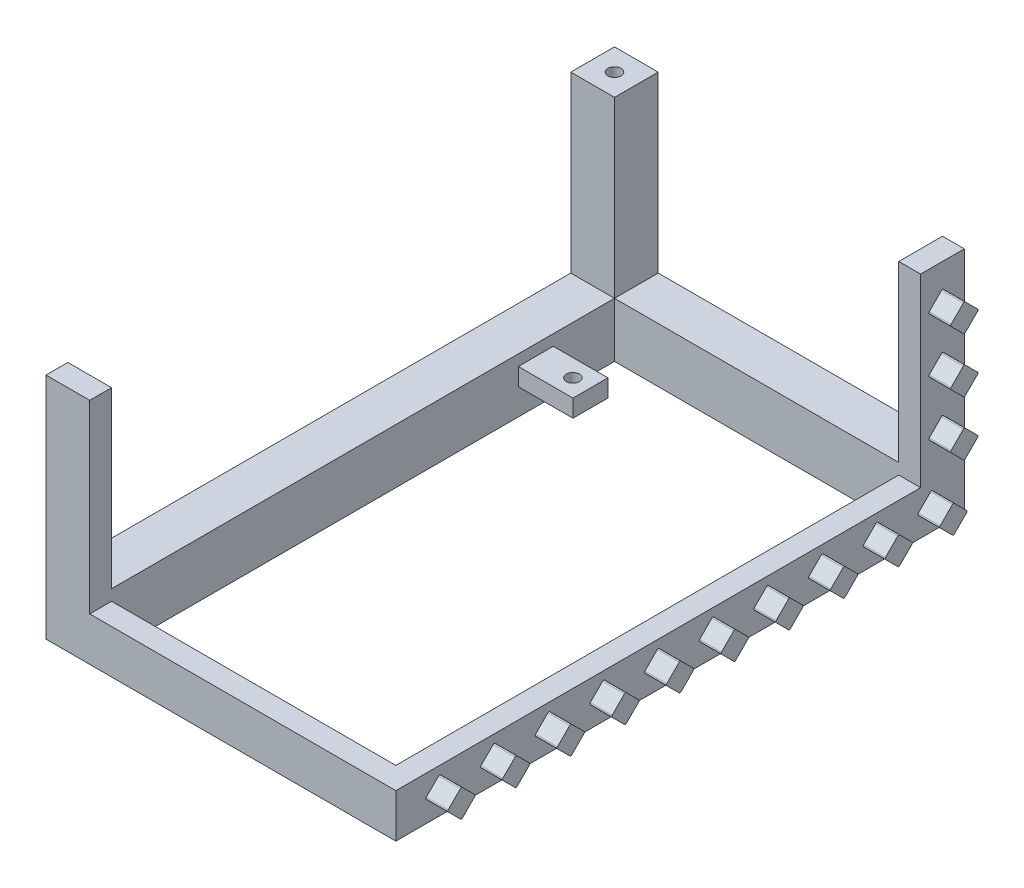
SolidWorks part; units mm, degrees
other "Markup1"
sketch "Sketch26" plane through (40, 52.3, 60) normal (0.2452, 0.2829, 0.9273) x (0.9695, -0.0685, -0.2355)
ref_plane "Front Plane" through (0, 0, 0) normal (0, 0, 1) x (1, 0, 0)
ref_plane "Top Plane" through (0, 0, 0) normal (0, 1, 0) x (1, 0, 0)
ref_plane "Right Plane" through (0, 0, 0) normal (1, 0, 0) x (0, 0, -1)
sketch "Sketch1" plane through (0, 0, 0) normal (0, 1, 0) x (1, 0, 0)
  line L0 (0, 0) -> (0, 70) construction
  line L1 (35, -60) -> (-45, -60)
  line L2 (35, -60) -> (35, 70)
  line L3 (35, 70) -> (-45, 70)
  line L4 (-45, -60) -> (-45, 70)
  line L5 (0, 0) -> (0, -60) construction
  point P0 (0, 0)
  dimension "D1" = 70
  dimension "D2" = 60
extrude "Boss-Extrude1" add sketch "Sketch1" along normal blind 10
sketch "Sketch9" plane through (0, 10, 0) normal (0, 1, 0) x (1, 0, 0)
  line L0 (35, 70) -> (-45, 70)
  line L1 (-45, 70) -> (-45, -60)
  line L2 (-45, -60) -> (-35, -60)
  line L3 (-45, -60) -> (35, -60) construction
  line L4 (35, 70) -> (35, 60)
  line L5 (35, -60) -> (35, 70) construction
  line L6 (35, 60) -> (-35, 60)
  line L7 (-35, -60) -> (-35, 60)
extrude "Boss-Extrude10" add sketch "Sketch9" along normal blind 42.3
sketch "Sketch13" plane through (-35, 0, 0) normal (1, 0, 0) x (0, 0, -1)
  line L5 (60, 52.3) -> (-55, 52.3)
  line L8 (-60, 52.3) -> (60, 52.3) construction
  line L11 (60, 12.5) -> (-55, 12.5)
  line L13 (60, 52.3) -> (60, 12.5)
  line L14 (-55, 52.3) -> (-55, 12.5)
  line L17 (-60, 52.3) -> (-60, 10) construction
  line M9 (-60, 10) -> (60, 10)
  line M12 (60, 10) -> (60, 52.3)
  line M13 (60, 52.3) -> (-60, 52.3)
  dimension "D1" = 5
extrude "Cut-Extrude3" cut sketch "Sketch13" against normal through all contours L14 M13 M9 M12 region at (-35, 32.4, -2.5)
sketch "Sketch14" plane through (0, 0, -60) normal (0, 0, 1) x (1, 0, 0)
  line L12 (-35, 12.5) -> (30, 12.5)
  line L13 (30, 12.5) -> (30, 52.3)
  line L14 (-45, 52.3) -> (35, 52.3) construction
  line L15 (30, 52.3) -> (-35, 52.3)
  line L16 (-35, 52.3) -> (-35, 12.5)
  line L17 (35, 52.3) -> (35, 10) construction
  dimension "D1" = 5
extrude "Cut-Extrude4" cut sketch "Sketch14" against normal through all
sketch "Sketch15" plane through (0, 52.3, 0) normal (0, 1, 0) x (1, 0, 0)
  line L0 (-40, 70) -> (-40, 65) construction
  line L1 (35, 70) -> (30, 70) construction
  line L2 (-40, 65) -> (-45, 65) construction
  line L3 (-45, 70) -> (-45, 60) construction
  line L4 (30, 60) -> (35, 60) construction
  circle A0 centre (-40, 65) radius 1.5
  dimension "D1" = 5
  dimension "D2" = 5
extrude "Cut-Extrude5" cut sketch "Sketch15" against normal blind 4
sketch "Sketch21" plane through (0, 10, 0) normal (0, 1, 0) x (1, 0, 0)
  line L0 (-26.5, 42) -> (-45, 42) construction
  line L1 (-26.5, 42) -> (-26.5, 70) construction
  line L2 (-35, 70) -> (30, 70) construction
  line L5 (-45, -55) -> (-45, 60) construction
  circle A0 centre (-26.5, 42) radius 1.5
extrude "Cut-Extrude8" cut sketch "Sketch21" against normal through all
sketch "Sketch22" plane through (35, 0, 0) normal (1, 0, 0) x (0, 0, -1)
  line L0 (-60, 5) -> (60, 5) construction
  line L1 (-60, 10) -> (-60, 0) construction
  line L2 (70, 52.3) -> (70, 0) construction
  line L3 (60, 10) -> (60, 0) construction
  line L41 (60, 10) -> (70, 10) construction
  line L42 (65, 10) -> (65, 52.3) construction
  line L43 (-60, 0) -> (70, 0) construction
  line L44 (60, 52.3) -> (70, 52.3) construction
  line L56 (68.25, 31.15) -> (61.75, 31.15) construction
  line L73 (0, 8.25) -> (0, 1.75) construction
  line L74 (-0.2121, 8.0379) -> (-3.0379, 5.2121)
  line L75 (-3.0379, 4.7879) -> (-0.2121, 1.9621)
  line L76 (0.2121, 1.9621) -> (3.0379, 4.7879)
  line L77 (3.0379, 5.2121) -> (0.2121, 8.0379)
  line L78 (15.5379, 5.2121) -> (12.7121, 8.0379)
  line L79 (12.2879, 8.0379) -> (9.4621, 5.2121)
  line L80 (9.4621, 4.7879) -> (12.2879, 1.9621)
  line L81 (12.7121, 1.9621) -> (15.5379, 4.7879)
  line L82 (28.0379, 5.2121) -> (25.2121, 8.0379)
  line L83 (24.7879, 8.0379) -> (21.9621, 5.2121)
  line L84 (21.9621, 4.7879) -> (24.7879, 1.9621)
  line L85 (25.2121, 1.9621) -> (28.0379, 4.7879)
  line L86 (40.5379, 5.2121) -> (37.7121, 8.0379)
  line L87 (37.2879, 8.0379) -> (34.4621, 5.2121)
  line L88 (34.4621, 4.7879) -> (37.2879, 1.9621)
  line L89 (37.7121, 1.9621) -> (40.5379, 4.7879)
  line L90 (53.0379, 5.2121) -> (50.2121, 8.0379)
  line L91 (49.7879, 8.0379) -> (46.9621, 5.2121)
  line L92 (46.9621, 4.7879) -> (49.7879, 1.9621)
  line L93 (50.2121, 1.9621) -> (53.0379, 4.7879)
  line L94 (65.5379, 5.2121) -> (62.7121, 8.0379)
  line L95 (62.2879, 8.0379) -> (59.4621, 5.2121)
  line L96 (59.4621, 4.7879) -> (62.2879, 1.9621)
  line L97 (62.7121, 1.9621) -> (65.5379, 4.7879)
  line L98 (-9.4621, 5.2121) -> (-12.2879, 8.0379)
  line L99 (-12.7121, 8.0379) -> (-15.5379, 5.2121)
  line L100 (-15.5379, 4.7879) -> (-12.7121, 1.9621)
  line L101 (-12.2879, 1.9621) -> (-9.4621, 4.7879)
  line L102 (-21.9621, 5.2121) -> (-24.7879, 8.0379)
  line L103 (-25.2121, 8.0379) -> (-28.0379, 5.2121)
  line L104 (-28.0379, 4.7879) -> (-25.2121, 1.9621)
  line L105 (-24.7879, 1.9621) -> (-21.9621, 4.7879)
  line L106 (-34.4621, 5.2121) -> (-37.2879, 8.0379)
  line L107 (-37.7121, 8.0379) -> (-40.5379, 5.2121)
  line L108 (-40.5379, 4.7879) -> (-37.7121, 1.9621)
  line L109 (-37.2879, 1.9621) -> (-34.4621, 4.7879)
  line L110 (-46.9621, 5.2121) -> (-49.7879, 8.0379)
  line L111 (-50.2121, 8.0379) -> (-53.0379, 5.2121)
  line L112 (-53.0379, 4.7879) -> (-50.2121, 1.9621)
  line L113 (-49.7879, 1.9621) -> (-46.9621, 4.7879)
  line L114 (61.9621, 31.3621) -> (64.7879, 34.1879)
  line L115 (65.2121, 34.1879) -> (68.0379, 31.3621)
  line L116 (68.0379, 30.9379) -> (65.2121, 28.1121)
  line L117 (64.7879, 28.1121) -> (61.9621, 30.9379)
  line L118 (64.7879, 40.6121) -> (61.9621, 43.4379)
  line L119 (61.9621, 43.8621) -> (64.7879, 46.6879)
  line L120 (65.2121, 46.6879) -> (68.0379, 43.8621)
  line L121 (68.0379, 43.4379) -> (65.2121, 40.6121)
  line L122 (64.7879, 15.6121) -> (61.9621, 18.4379)
  line L123 (61.9621, 18.8621) -> (64.7879, 21.6879)
  line L124 (65.2121, 21.6879) -> (68.0379, 18.8621)
  line L125 (68.0379, 18.4379) -> (65.2121, 15.6121)
  arc A56 (-3.0379, 5.2121) -> (-3.0379, 4.7879) centre (-2.8257, 5) ccw
  arc A57 (0.2121, 1.9621) -> (-0.2121, 1.9621) centre (0, 2.1743) cw
  arc A58 (3.0379, 4.7879) -> (3.0379, 5.2121) centre (2.8257, 5) ccw
  arc A59 (0.2121, 8.0379) -> (-0.2121, 8.0379) centre (0, 7.8257) ccw
  arc A60 (12.7121, 8.0379) -> (12.2879, 8.0379) centre (12.5, 7.8257) ccw
  arc A61 (15.5379, 4.7879) -> (15.5379, 5.2121) centre (15.3257, 5) ccw
  arc A62 (9.4621, 5.2121) -> (9.4621, 4.7879) centre (9.6743, 5) ccw
  arc A63 (12.7121, 1.9621) -> (12.2879, 1.9621) centre (12.5, 2.1743) cw
  arc A64 (25.2121, 8.0379) -> (24.7879, 8.0379) centre (25, 7.8257) ccw
  arc A65 (28.0379, 4.7879) -> (28.0379, 5.2121) centre (27.8257, 5) ccw
  arc A66 (21.9621, 5.2121) -> (21.9621, 4.7879) centre (22.1743, 5) ccw
  arc A67 (25.2121, 1.9621) -> (24.7879, 1.9621) centre (25, 2.1743) cw
  arc A68 (37.7121, 8.0379) -> (37.2879, 8.0379) centre (37.5, 7.8257) ccw
  arc A69 (40.5379, 4.7879) -> (40.5379, 5.2121) centre (40.3257, 5) ccw
  arc A70 (34.4621, 5.2121) -> (34.4621, 4.7879) centre (34.6743, 5) ccw
  arc A71 (37.7121, 1.9621) -> (37.2879, 1.9621) centre (37.5, 2.1743) cw
  arc A72 (50.2121, 8.0379) -> (49.7879, 8.0379) centre (50, 7.8257) ccw
  arc A73 (53.0379, 4.7879) -> (53.0379, 5.2121) centre (52.8257, 5) ccw
  arc A74 (46.9621, 5.2121) -> (46.9621, 4.7879) centre (47.1743, 5) ccw
  arc A75 (50.2121, 1.9621) -> (49.7879, 1.9621) centre (50, 2.1743) cw
  arc A76 (62.7121, 8.0379) -> (62.2879, 8.0379) centre (62.5, 7.8257) ccw
  arc A77 (65.5379, 4.7879) -> (65.5379, 5.2121) centre (65.3257, 5) ccw
  arc A78 (59.4621, 5.2121) -> (59.4621, 4.7879) centre (59.6743, 5) ccw
  arc A79 (62.7121, 1.9621) -> (62.2879, 1.9621) centre (62.5, 2.1743) cw
  arc A80 (-12.2879, 8.0379) -> (-12.7121, 8.0379) centre (-12.5, 7.8257) ccw
  arc A81 (-9.4621, 4.7879) -> (-9.4621, 5.2121) centre (-9.6743, 5) ccw
  arc A82 (-15.5379, 5.2121) -> (-15.5379, 4.7879) centre (-15.3257, 5) ccw
  arc A83 (-12.2879, 1.9621) -> (-12.7121, 1.9621) centre (-12.5, 2.1743) cw
  arc A84 (-24.7879, 8.0379) -> (-25.2121, 8.0379) centre (-25, 7.8257) ccw
  arc A85 (-21.9621, 4.7879) -> (-21.9621, 5.2121) centre (-22.1743, 5) ccw
  arc A86 (-28.0379, 5.2121) -> (-28.0379, 4.7879) centre (-27.8257, 5) ccw
  arc A87 (-24.7879, 1.9621) -> (-25.2121, 1.9621) centre (-25, 2.1743) cw
  arc A88 (-37.2879, 8.0379) -> (-37.7121, 8.0379) centre (-37.5, 7.8257) ccw
  arc A89 (-34.4621, 4.7879) -> (-34.4621, 5.2121) centre (-34.6743, 5) ccw
  arc A90 (-40.5379, 5.2121) -> (-40.5379, 4.7879) centre (-40.3257, 5) ccw
  arc A91 (-37.2879, 1.9621) -> (-37.7121, 1.9621) centre (-37.5, 2.1743) cw
  arc A92 (-49.7879, 8.0379) -> (-50.2121, 8.0379) centre (-50, 7.8257) ccw
  arc A93 (-46.9621, 4.7879) -> (-46.9621, 5.2121) centre (-47.1743, 5) ccw
  arc A94 (-53.0379, 5.2121) -> (-53.0379, 4.7879) centre (-52.8257, 5) ccw
  arc A95 (-49.7879, 1.9621) -> (-50.2121, 1.9621) centre (-50, 2.1743) cw
  arc A96 (61.9621, 30.9379) -> (61.9621, 31.3621) centre (62.1743, 31.15) cw
  arc A97 (65.2121, 28.1121) -> (64.7879, 28.1121) centre (65, 28.3243) cw
  arc A98 (68.0379, 30.9379) -> (68.0379, 31.3621) centre (67.8257, 31.15) ccw
  arc A99 (64.7879, 34.1879) -> (65.2121, 34.1879) centre (65, 33.9757) cw
  arc A100 (65.2121, 40.6121) -> (64.7879, 40.6121) centre (65, 40.8243) cw
  arc A101 (61.9621, 43.4379) -> (61.9621, 43.8621) centre (62.1743, 43.65) cw
  arc A102 (64.7879, 46.6879) -> (65.2121, 46.6879) centre (65, 46.4757) cw
  arc A103 (68.0379, 43.4379) -> (68.0379, 43.8621) centre (67.8257, 43.65) ccw
  arc A104 (65.2121, 15.6121) -> (64.7879, 15.6121) centre (65, 15.8243) cw
  arc A105 (61.9621, 18.4379) -> (61.9621, 18.8621) centre (62.1743, 18.65) cw
  arc A106 (64.7879, 21.6879) -> (65.2121, 21.6879) centre (65, 21.4757) cw
  arc A107 (68.0379, 18.4379) -> (68.0379, 18.8621) centre (67.8257, 18.65) ccw
  point P12 (0, 5)
  point P16 (-3.25, 5)
  point P22 (3.25, 5)
  point P132 (65, 31.15)
  point P135 (65, 27.9)
  point P141 (65, 34.4)
  dimension "D1" = 0.3
  dimension "D4" = 0.3
  dimension "D2" = 6
  dimension "D3" = 5
  dimension "D5" = 2
  dimension "D6" = 2
extrude "Boss-Extrude11" add sketch "Sketch22" along normal blind 5
sketch "Sketch23" plane through (0, 10, 0) normal (0, 1, 0) x (1, 0, 0)
  line L2 (30, -55) -> (-35, -55)
  line L3 (-35, -60) -> (-35, 60) construction
  line L5 (-35, 60) -> (30, 60)
  line L7 (-22.5, 38) -> (-22.5, 46)
  line L10 (-35, 60) -> (-35, 46)
  line L11 (-35, 46) -> (-22.5, 46)
  line L12 (-22.5, 38) -> (-35, 38)
  line L13 (-35, 38) -> (-35, -55)
  line L14 (30, 60) -> (30, -55)
  circle A0 centre (-26.5, 42) radius 1.5 construction
  dimension "D1" = 4
  dimension "D2" = 4
  dimension "D3" = 4
extrude "Cut-Extrude9" cut sketch "Sketch23" against normal through all
sketch "Sketch24" plane through (0, 0, 0) normal (0, -1, 0) x (1, 0, 0)
  circle A0 centre (-40, -65) radius 1.5 construction
  circle A1 centre (-40, -65) radius 1.5
extrude "Cut-Extrude10" cut sketch "Sketch24" against normal blind 4
sketch "Sketch25" plane through (0, 0, 0) normal (0, -1, 0) x (1, 0, 0)
  line L0 (-22.5, -38) -> (-22.5, -46)
  line L1 (-22.5, -46) -> (-35, -46)
  line L2 (-35, -46) -> (-35, -38)
  line L3 (-35, -38) -> (-22.5, -38)
extrude "Cut-Extrude11" cut sketch "Sketch25" against normal blind 6
